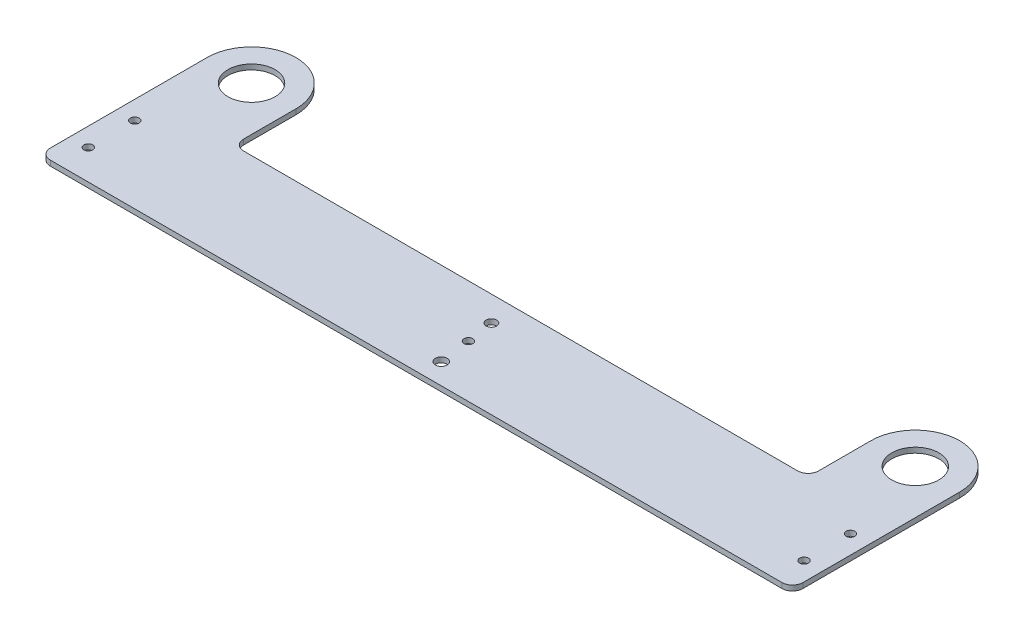
SolidWorks part; units mm, degrees
material "6063-T6"
ref_plane "Front" through (0, 0, 0) normal (0, 0, 1) x (1, 0, 0)
ref_plane "Top" through (0, 0, 0) normal (0, 1, 0) x (1, 0, 0)
ref_plane "Right" through (0, 0, 0) normal (1, 0, 0) x (0, 0, -1)
sketch "Sketch1" plane through (0, 0, 0) normal (0, 1, 0) x (1, 0, 0)
  line L0 (0, 0) -> (403.225, 0) construction
  line L5 (-26.9875, 0) -> (-26.9875, -95.25)
  line L6 (430.2125, 0) -> (430.2125, -95.25)
  line L7 (423.8625, -101.6) -> (-20.6375, -101.6)
  line L8 (26.9875, 0) -> (26.9875, -31.75)
  line L9 (376.2375, 0) -> (376.2375, -31.75)
  line L10 (369.8875, -38.1) -> (33.3375, -38.1)
  line L11 (403.225, 0) -> (403.225, 26.9875) construction
  circle A0 centre (0, 0) radius 14.2875
  circle A1 centre (403.225, 0) radius 14.2875
  arc A2 (26.9875, 0) -> (-26.9875, 0) centre (0, 0) ccw
  arc A3 (430.2125, 0) -> (376.2375, 0) centre (403.225, 0) ccw
  circle A4 centre (0, 0) radius 26.9875 construction
  circle A5 centre (403.225, 0) radius 26.9875 construction
  arc A6 (376.2375, -31.75) -> (369.8875, -38.1) centre (369.8875, -31.75) cw
  arc A7 (430.2125, -95.25) -> (423.8625, -101.6) centre (423.8625, -95.25) cw
  arc A8 (-26.9875, -95.25) -> (-20.6375, -101.6) centre (-20.6375, -95.25) ccw
  arc A9 (26.9875, -31.75) -> (33.3375, -38.1) centre (33.3375, -31.75) ccw
  point P24 (-26.9875, -101.6)
  point P27 (26.9875, -38.1)
  dimension "D3" = 28.575
  dimension "D5" = 28.575
  dimension "D7" = 6.35
  dimension "D9" = 128.5875
  dimension "D1" = 12.7
  dimension "D2" = 101.6
  dimension "D4" = 403.225
  dimension "D6" = 38.1
  dimension "D8" = 457.2
extrude "Boss-Extrude1" add sketch "Sketch1" along normal blind 3.175
sketch "Sketch2" plane through (0, 3.175, 0) normal (0, 1, 0) x (1, 0, 0)
  line L1 (-26.9875, 0) -> (-26.9875, -95.25) construction
  line L2 (-20.6375, -101.6) -> (423.8625, -101.6) construction
  line L3 (430.2125, -95.25) -> (430.2125, 0) construction
  circle A1 centre (204.1525, -88.9) radius 3.556
  circle A3 centre (199.0725, -53.34) radius 3.175
  dimension "D3" = 231.14
  dimension "D1" = 231.14
  dimension "D2" = 12.7
  dimension "D4" = 48.26
extrude "Cut-Extrude1" cut sketch "Sketch2" against normal up to next
sketch "Sketch3" plane through (0, 3.175, 0) normal (0, 1, 0) x (1, 0, 0)
  line L0 (201.6125, -38.1) -> (201.6125, 7.4644) construction
  line L1 (369.8875, -38.1) -> (33.3375, -38.1) construction
  circle A1 centre (-15.7797, -55.159) radius 2.667
  circle A2 centre (419.0047, -55.159) radius 2.667
  circle A3 centre (-15.7797, -83.3715) radius 2.667
  circle A4 centre (419.0047, -83.3715) radius 2.667
  dimension "D1" = 5.334
extrude "Cut-Extrude2" cut sketch "Sketch3" against normal up to next
sketch "Sketch4" plane through (0, 3.175, 0) normal (0, 1, 0) x (1, 0, 0)
  line L0 (201.6125, -38.1) -> (201.6125, -101.6) construction
  line L1 (369.8875, -38.1) -> (33.3375, -38.1) construction
  line L2 (-20.6375, -101.6) -> (423.8625, -101.6) construction
  circle A0 centre (201.6125, -69.85) radius 2.667
  dimension "D1" = 5.334
extrude "Cut-Extrude3" cut sketch "Sketch4" against normal up to next
